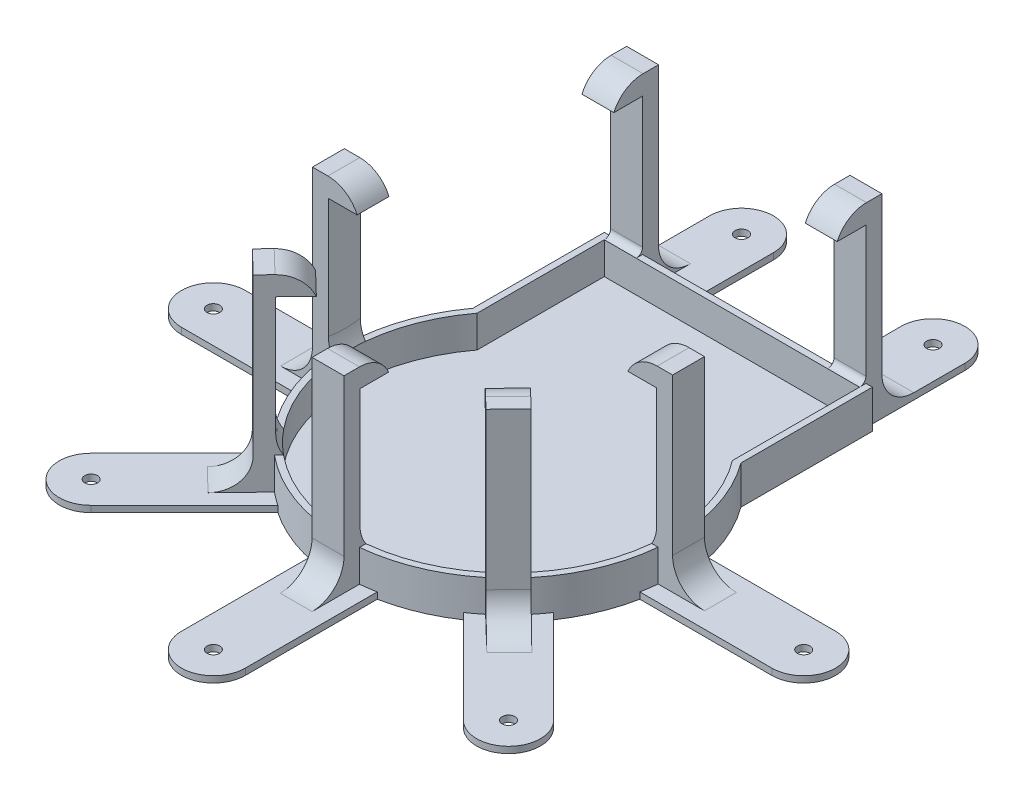
SolidWorks part; units mm, degrees
ref_plane "Front Plane" through (0, 0, 0) normal (0, 0, 1) x (1, 0, 0)
ref_plane "Top Plane" through (0, 0, 0) normal (0, 1, 0) x (1, 0, 0)
ref_plane "Right Plane" through (0, 0, 0) normal (1, 0, 0) x (0, 0, -1)
sketch "Sketch1" plane through (0, 0, 0) normal (0, 1, 0) x (1, 0, 0)
  line L2 (40, 33.3828) -> (40, 70) construction
  line L3 (40, 70) -> (-40, 70) construction
  line L4 (-40, 33.3828) -> (-40, 70) construction
  line L6 (-42, 72) -> (42, 72)
  line L7 (-42, 72) -> (-42, 30.8287)
  line L9 (42, 72) -> (42, 30.8287)
  arc A0 (-42, 30.8287) -> (42, 30.8287) centre (0, 0) ccw
  arc A1 (-40, 33.3828) -> (-42, 30.8287) centre (0, 0) ccw construction
  arc A2 (42, 30.8287) -> (40, 33.3828) centre (0, 0) ccw construction
  dimension "D1" = 104.2
  dimension "D2" = 2
  dimension "D3" = 2
  dimension "D4" = 2
extrude "Boss-Extrude1" add sketch "Sketch1" along normal blind 2
sketch "Sketch2" plane through (0, 0, 0) normal (0, -1, 0) x (1, 0, 0)
  circle A0 centre (0, 0) radius 29.426
sketch "Sketch3" plane through (0, 2, 0) normal (0, 1, 0) x (1, 0, 0)
  line L1 (-42, 72) -> (42, 72)
  line L2 (-42, 72) -> (-42, 30.8287)
  line L4 (42, 72) -> (42, 30.8287)
  line L5 (-40, 70) -> (40, 70)
  line L6 (-40, 70) -> (-40, 30.1664)
  line L8 (40, 70) -> (40, 30.1664)
  arc A0 (-42, 30.8287) -> (42, 30.8287) centre (0, 0) ccw
  arc A1 (-40, 30.1664) -> (40, 30.1664) centre (0, 0) ccw
  dimension "D1" = 2
  dimension "D2" = 104.2
  dimension "D3" = 2
  dimension "D4" = 2
  dimension "D5" = 2
extrude "Boss-Extrude2" add sketch "Sketch3" along normal blind 10
sketch "Sketch4" plane through (0, 2, 0) normal (0, 1, 0) x (1, 0, 0)
  line L0 (0, 90.6986) -> (0, 63) construction
  line L1 (-102.4496, 0) -> (-90.5, 0) construction
  line L2 (-77.3185, -77.3185) -> (0, 0) construction
  line L3 (0, 0) -> (19.4454, -19.4454) construction
  line L4 (0, 80.5846) -> (42, 80.5846) construction
  line L5 (0, 80.5846) -> (-42, 80.5846) construction
  line L6 (30, 95.1516) -> (30, 27.3272) construction
  line L7 (-30, 95.1516) -> (-30, 27.3272) construction
  line L8 (-37.5, 0) -> (-92.5, 0) construction
  line L9 (-37.5, -10) -> (-92.5, -10)
  line L10 (-37.5, 10) -> (-92.5, 10)
  line L11 (0, -37.5) -> (0, -92.5) construction
  line L12 (10, -37.5) -> (10, -92.5)
  line L13 (-10, -37.5) -> (-10, -92.5)
  line L14 (-26.5165, -26.5165) -> (-65.4074, -65.4074) construction
  line L15 (-19.4454, -33.5876) -> (-58.3363, -72.4784)
  line L16 (-33.5876, -19.4454) -> (-72.4784, -58.3363)
  line L17 (26.5165, -26.5165) -> (65.4074, -65.4074) construction
  line L18 (33.5876, -19.4454) -> (72.4784, -58.3363)
  line L19 (19.4454, -33.5876) -> (58.3363, -72.4784)
  line L20 (37.5, 0) -> (92.5, 0) construction
  line L21 (37.5, 10) -> (92.5, 10)
  line L22 (37.5, -10) -> (92.5, -10)
  line L23 (30, 103) -> (30, 63) construction
  line L24 (40, 103) -> (40, 63)
  line L25 (20, 103) -> (20, 63)
  line L26 (-30, 103) -> (-30, 63) construction
  line L27 (-20, 103) -> (-20, 63)
  line L28 (-40, 103) -> (-40, 63)
  line L29 (-40, 63) -> (40, 63) construction
  line L30 (-40, 70) -> (-40, 30.1664) construction
  line L31 (40, 30.1664) -> (40, 70) construction
  line L32 (40, 70) -> (-40, 70) construction
  line L33 (19.4454, -19.4454) -> (26.5165, -26.5165) construction
  line L34 (26.5165, -26.5165) -> (74.7023, -74.7023) construction
  line L35 (0, 63) -> (0, 37.5) construction
  line L36 (0, 37.5) -> (0, -82.0383) construction
  line L37 (-90.5, 0) -> (-37.5, 0) construction
  line L38 (-37.5, 0) -> (112.3735, 0) construction
  line L39 (-40, 70) -> (-40, 30.1664) construction
  arc A0 (-37.5, -10) -> (-37.5, 10) centre (-37.5, 0) ccw
  arc A1 (-92.5, 10) -> (-92.5, -10) centre (-92.5, 0) ccw
  arc A2 (10, -37.5) -> (-10, -37.5) centre (0, -37.5) ccw
  arc A3 (-10, -92.5) -> (10, -92.5) centre (0, -92.5) ccw
  arc A4 (-19.4454, -33.5876) -> (-33.5876, -19.4454) centre (-26.5165, -26.5165) ccw
  arc A5 (-72.4784, -58.3363) -> (-58.3363, -72.4784) centre (-65.4074, -65.4074) ccw
  arc A6 (33.5876, -19.4454) -> (19.4454, -33.5876) centre (26.5165, -26.5165) ccw
  arc A7 (58.3363, -72.4784) -> (72.4784, -58.3363) centre (65.4074, -65.4074) ccw
  arc A8 (37.5, 10) -> (37.5, -10) centre (37.5, 0) ccw
  arc A9 (92.5, -10) -> (92.5, 10) centre (92.5, 0) ccw
  arc A10 (40, 103) -> (20, 103) centre (30, 103) ccw
  arc A11 (20, 63) -> (40, 63) centre (30, 63) ccw
  arc A12 (-20, 103) -> (-40, 103) centre (-30, 103) ccw
  arc A13 (-40, 63) -> (-20, 63) centre (-30, 63) ccw
  arc A14 (9.9107, -36.1667) -> (18.5658, -32.5816) centre (0, 0) ccw construction
  circle A15 centre (-92.5, 0) radius 2
  circle A16 centre (-65.4074, -65.4074) radius 2
  circle A17 centre (0, -92.5) radius 2
  circle A18 centre (65.4074, -65.4074) radius 2
  circle A19 centre (92.5, 0) radius 2
  circle A20 centre (30, 103) radius 2
  circle A21 centre (-30, 103) radius 2
  arc A22 (-18.5658, -32.5816) -> (-9.9107, -36.1667) centre (0, 0) ccw construction
  arc A23 (-9.9107, -36.1667) -> (0, -37.5) centre (0, 0) ccw construction
  arc A24 (0, -37.5) -> (9.9107, -36.1667) centre (0, 0) ccw construction
  arc A25 (26.5165, -26.5165) -> (32.5816, -18.5658) centre (0, 0) ccw construction
  arc A26 (32.5816, -18.5658) -> (36.1667, -9.9107) centre (0, 0) ccw construction
  arc A27 (18.5658, -32.5816) -> (26.5165, -26.5165) centre (0, 0) ccw construction
  arc A28 (36.1667, -9.9107) -> (37.5, 0) centre (0, 0) ccw construction
  arc A29 (-36.1667, -9.9107) -> (-32.5816, -18.5658) centre (0, 0) ccw construction
  arc A30 (37.5, 0) -> (36.1667, 9.9107) centre (0, 0) ccw construction
  arc A31 (36.1667, 9.9107) -> (30, 22.5) centre (0, 0) ccw construction
  arc A32 (30, 22.5) -> (0, 37.5) centre (0, 0) ccw construction
  arc A33 (0, 37.5) -> (-30, 22.5) centre (0, 0) ccw construction
  arc A34 (-30, 22.5) -> (-36.1667, 9.9107) centre (0, 0) ccw construction
  arc A35 (-36.1667, 9.9107) -> (-37.5, 0) centre (0, 0) ccw construction
  arc A36 (-37.5, 0) -> (-36.1667, -9.9107) centre (0, 0) ccw construction
  arc A37 (-32.5816, -18.5658) -> (-26.5165, -26.5165) centre (0, 0) ccw construction
  arc A38 (-26.5165, -26.5165) -> (-18.5658, -32.5816) centre (0, 0) ccw construction
  point P17 (-65, 0)
  point P22 (0, -65)
  point P29 (-45.9619, -45.9619)
  point P36 (45.9619, -45.9619)
  point P43 (65, 0)
  point P50 (30, 83)
  point P57 (-30, 83)
  dimension "D17" = 75
  dimension "D18" = 4
  dimension "D19" = 4
  dimension "D20" = 4
  dimension "D21" = 4
  dimension "D22" = 4
  dimension "D23" = 4
  dimension "D24" = 4
  dimension "D1" = 45
  dimension "D2" = 45
  dimension "D3" = 20
  dimension "D4" = 55
  dimension "D5" = 55
  dimension "D6" = 55
  dimension "D7" = 55
  dimension "D8" = 55
  dimension "D9" = 40
  dimension "D10" = 40
  dimension "D11" = 20
  dimension "D12" = 20
  dimension "D13" = 20
  dimension "D14" = 20
  dimension "D15" = 20
  dimension "D16" = 20
  dimension "D25" = 7
  dimension "D26" = 0
  dimension "D27" = 0
extrude "Boss-Extrude3" add sketch "Sketch4" against normal blind 2
sketch "Sketch6" plane through (0, 2, 0) normal (0, 1, 0) x (1, 0, 0)
  line L0 (-33.0087, -39.9501) -> (-40.2072, -33.0087)
  line L1 (-40, 72) -> (-30, 72)
  line L2 (-40, 72) -> (-40, 77)
  line L3 (-40, 77) -> (-30, 77)
  line L4 (-30, 72) -> (-30, 77)
  line L5 (40, 72) -> (30, 72)
  line L6 (40, 72) -> (40, 77)
  line L7 (40, 77) -> (30, 77)
  line L8 (30, 72) -> (30, 77)
  line L9 (-56.4585, 5) -> (-51.4585, 5)
  line L10 (-56.4585, 5) -> (-56.4585, -5)
  line L11 (-56.4585, -5) -> (-51.4585, -5)
  line L12 (-51.4585, 5) -> (-51.4585, -5)
  line L13 (-4.8667, -51.7033) -> (5.1333, -51.7033)
  line L14 (-4.8667, -51.7033) -> (-4.8667, -56.7033)
  line L15 (-4.8667, -56.7033) -> (5.1333, -56.7033)
  line L16 (5.1333, -51.7033) -> (5.1333, -56.7033)
  line L17 (51.4049, 5) -> (56.4049, 5)
  line L18 (51.4049, 5) -> (51.4049, -5)
  line L19 (51.4049, -5) -> (56.4049, -5)
  line L20 (56.4049, 5) -> (56.4049, -5)
  line L21 (-33.0087, -39.9501) -> (-36.4794, -43.5493)
  line L22 (-40.2072, -33.0087) -> (-43.6778, -36.6079)
  line L23 (-36.4794, -43.5493) -> (-43.6778, -36.6079)
  line L24 (32.8773, -40.0757) -> (39.8186, -32.8773)
  line L25 (32.8773, -40.0757) -> (36.4765, -43.5464)
  line L26 (39.8186, -32.8773) -> (43.4178, -36.3479)
  line L27 (36.4765, -43.5464) -> (43.4178, -36.3479)
  line L28 (0, -92.5) -> (0, -78.4073) construction
  line L29 (65.4074, -65.4074) -> (26.0253, -26.0253) construction
  line L30 (92.5, 0) -> (69.8665, 0) construction
  line L31 (-92.5, 0) -> (-74.916, 0) construction
  line L32 (-65.4074, -65.4074) -> (-30.7132, -30.7132) construction
  point P47 (-40.0786, -40.0786)
  point P49 (39.9472, -39.9472)
  point P50 (56.4049, 0)
  point P52 (-56.4585, 0)
  dimension "D1" = 10
  dimension "D2" = 10
  dimension "D3" = 5
  dimension "D4" = 5
  dimension "D5" = 10
  dimension "D6" = 5
  dimension "D7" = 45
  dimension "D8" = 45
extrude "Boss-Extrude4" add sketch "Sketch6" along normal blind 53
sketch "Sketch7" plane through (0, 55, 0) normal (0, 1, 0) x (1, 0, 0)
  line L0 (-36.4794, -43.5493) -> (-43.6778, -36.6079)
  line L1 (5.1333, -56.7033) -> (-4.8667, -56.7033)
  line L2 (5.1333, -56.7033) -> (5.1333, -42.7033)
  line L3 (5.1333, -42.7033) -> (-4.8667, -42.7033)
  line L4 (-4.8667, -56.7033) -> (-4.8667, -42.7033)
  line L5 (56.4049, 5) -> (42.4049, 5)
  line L6 (56.4049, 5) -> (56.4049, -5)
  line L7 (56.4049, -5) -> (42.4049, -5)
  line L8 (42.4049, 5) -> (42.4049, -5)
  line L9 (-56.4585, 5) -> (-42.4585, 5)
  line L10 (-56.4585, 5) -> (-56.4585, -5)
  line L11 (-56.4585, -5) -> (-42.4585, -5)
  line L12 (-42.4585, 5) -> (-42.4585, -5)
  line L13 (-40, 77) -> (-30, 77)
  line L14 (-40, 77) -> (-40, 63)
  line L15 (-40, 63) -> (-30, 63)
  line L16 (-30, 77) -> (-30, 63)
  line L17 (40, 77) -> (30, 77)
  line L18 (40, 77) -> (40, 63)
  line L19 (40, 63) -> (30, 63)
  line L20 (30, 77) -> (30, 63)
  line L21 (-36.4794, -43.5493) -> (-26.7615, -33.4715)
  line L22 (-43.6778, -36.6079) -> (-33.96, -26.5301)
  line L23 (-26.7615, -33.4715) -> (-33.96, -26.5301)
  line L24 (36.4765, -43.5464) -> (43.4178, -36.3479)
  line L25 (36.4765, -43.5464) -> (26.3987, -33.8285)
  line L26 (43.4178, -36.3479) -> (33.34, -26.63)
  line L27 (26.3987, -33.8285) -> (33.34, -26.63)
  dimension "D1" = 10
  dimension "D2" = 14
  dimension "D3" = 10
  dimension "D4" = 14
  dimension "D5" = 14
  dimension "D6" = 10
  dimension "D7" = 14
  dimension "D8" = 14
  dimension "D9" = 10
  dimension "D10" = 10
  dimension "D11" = 14
  dimension "D12" = 14
extrude "Boss-Extrude5" add sketch "Sketch7" along normal blind 6
fillet "Fillet1" radius 10 7 edges at (-42.4585, 61, 0) (-35, 61, -63) (35, 61, -63) (42.4049, 61, 0) (29.8693, 61, 30.2293) (0.1333, 61, 42.7033) (-30.3607, 61, 30.0008)
fillet "Fillet3" radius 10 5 edges at (51.4049, 12, 0) (36.3479, 12, 36.4765) (0.1333, 12, 51.7033) (-36.6079, 12, 36.4794) (-51.4585, 12, 0)
fillet "Fillet4" radius 10 7 edges at (35, 2, -77) (-35, 2, -77) (-56.4585, 2, 0) (-40.0786, 2, 40.0786) (0.1333, 2, 56.7033) (39.9472, 2, 39.9472) (56.4049, 2, 0)
fillet "Fillet6" radius 2 2 edges at (35, 12, -72) (-35, 12, -72)
